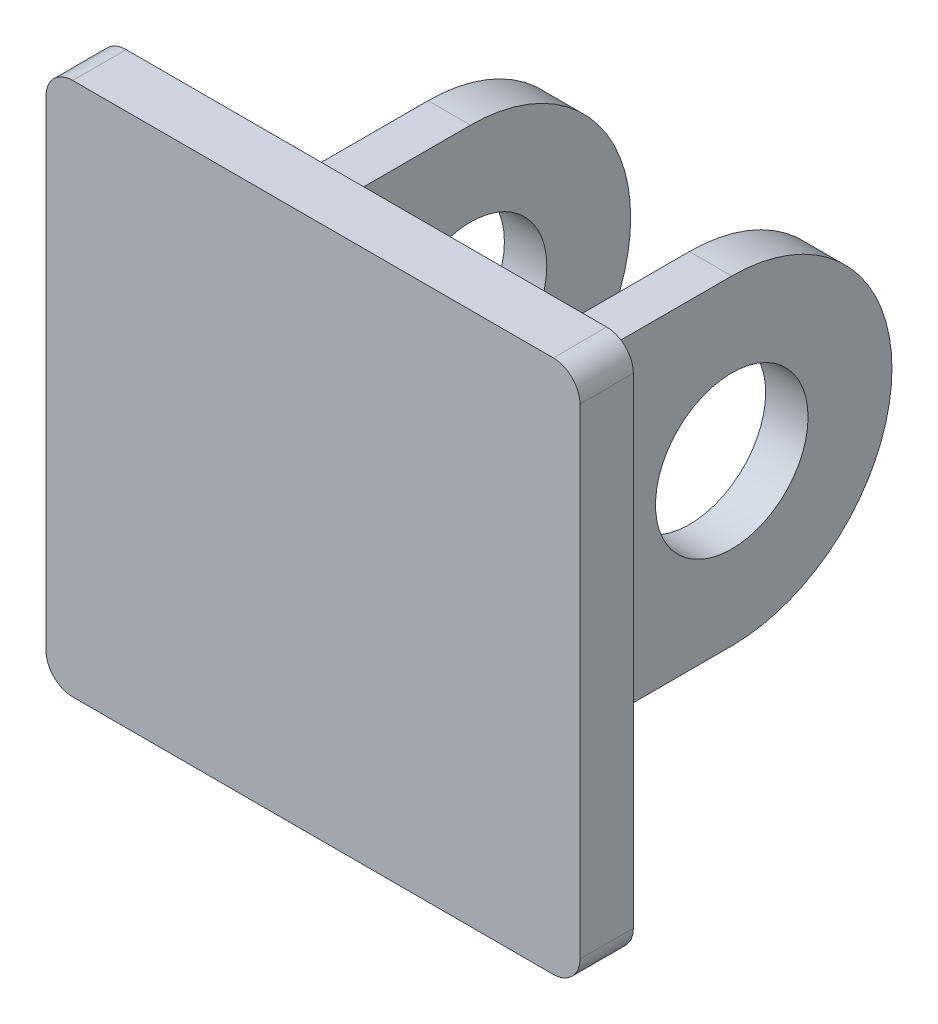
SolidWorks part; units mm, degrees
ref_plane "Front Plane" through (0, 0, 0) normal (0, 0, 1) x (1, 0, 0)
ref_plane "Top Plane" through (0, 0, 0) normal (0, 1, 0) x (1, 0, 0)
ref_plane "Right Plane" through (0, 0, 0) normal (1, 0, 0) x (0, 0, -1)
sketch "Sketch2" plane through (0, 0, 0) normal (0, 0, 1) x (1, 0, 0)
  line L1 (50, 50) -> (-50, 50)
  line L2 (50, 50) -> (50, -50)
  line L3 (50, -50) -> (-50, -50)
  line L4 (-50, 50) -> (-50, -50)
  line L5 (50, 50) -> (-50, -50) construction
  line L6 (50, -50) -> (-50, 50) construction
  point P0 (0, 0)
  dimension "D1" = 100
extrude "Boss-Extrude1" add sketch "Sketch2" along normal blind 10
ref_plane "Plane1" through (20.5, 0, 0) normal (1, 0, 0) x (0, 0, -1)
sketch "Sketch3" plane through (20.5, 0, 0) normal (1, 0, 0) x (0, 0, -1)
  line L1 (0, 30) -> (40, 30)
  line L2 (0, 30) -> (0, -30)
  line L3 (0, -30) -> (40, -30)
  line L4 (40, 30) -> (40, -30) construction
  line L5 (0, -50) -> (0, 50) construction
  arc A0 (40, 30) -> (40, -30) centre (40, 0) cw
  circle A1 centre (40, 0) radius 14.2875
  point P4 (0, 0)
  dimension "D1" = 30
  dimension "D3" = 28.575
  dimension "D2" = 40
extrude "Boss-Extrude2" add sketch "Sketch3" along normal blind 7.9375
mirror "Mirror1" about plane through (0, 0, 0) normal (1, 0, 0) of "Boss-Extrude2"
ref_axis "Axis1" through (0, 0, 14) along (0, 0, -1)
fillet "Fillet1" radius 5 4 edges at (-50, -50, 5) (-50, 50, 5) (50, -50, 5) (50, 50, 5)
